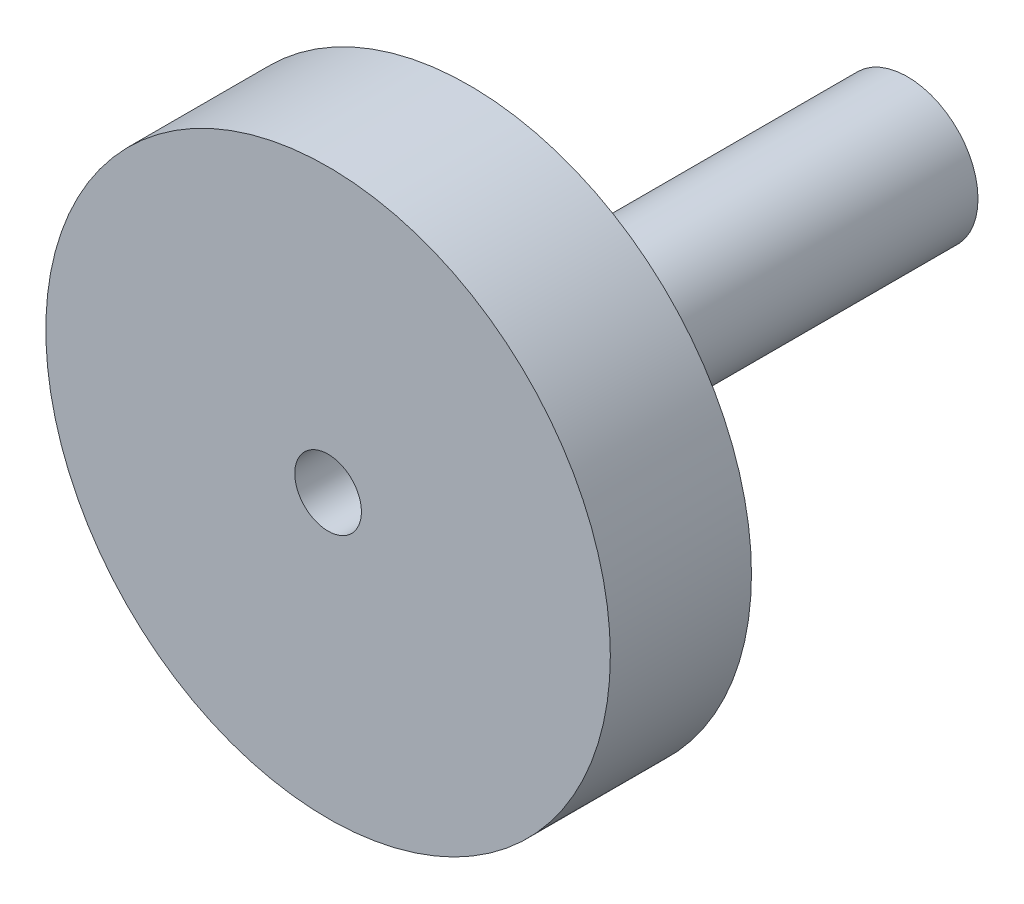
SolidWorks part; units mm, degrees
material "6061-T6 (SS)"
ref_plane "Front Plane" through (0, 0, 0) normal (0, 0, 1) x (1, 0, 0)
ref_plane "Top Plane" through (0, 0, 0) normal (0, 1, 0) x (1, 0, 0)
ref_plane "Right Plane" through (0, 0, 0) normal (1, 0, 0) x (0, 0, -1)
sketch "Sketch1" plane through (0, 0, 0) normal (1, 0, 0) x (0, 0, -1)
  line L1 (0, 0) -> (-3.175, 0)
  line L2 (3.175, 3.175) -> (3.175, 12.7)
  line L3 (3.175, 12.7) -> (-3.175, 12.7)
  line L4 (-3.175, 0) -> (-3.175, 12.7)
  line L5 (0, 0) -> (22.8917, 0)
  line L7 (3.175, 3.175) -> (22.8917, 3.175)
  line L8 (22.8917, 0) -> (22.8917, 3.175)
  dimension "D1" = 12.7
  dimension "D2" = 6.35
  dimension "D3" = 3.175
  dimension "D4" = 19.7167
revolve "Revolve1" add sketch "Sketch1" angle 360 about L5
sketch "Sketch2" plane through (0, 0, 3.175) normal (0, 0, 1) x (1, 0, 0)
  circle A0 centre (0, 0) radius 1.5
  dimension "D1" = 3
extrude "Cut-Extrude1" cut sketch "Sketch2" against normal blind 9.525
